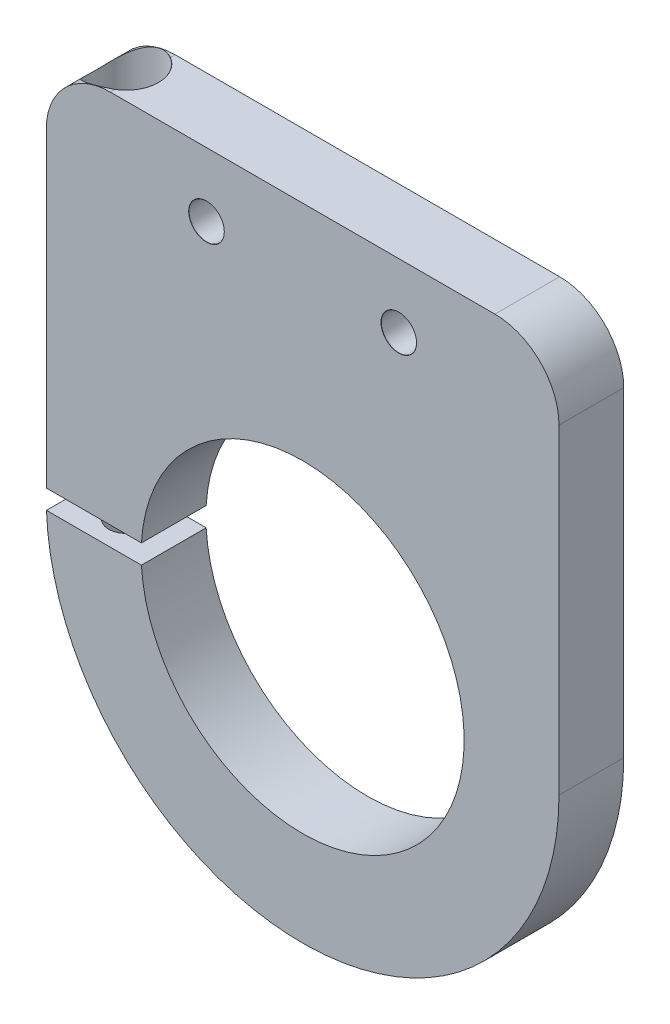
SolidWorks part; units mm, degrees
ref_plane "Front Plane" through (0, 0, 0) normal (0, 0, 1) x (1, 0, 0)
ref_plane "Top Plane" through (0, 0, 0) normal (0, 1, 0) x (1, 0, 0)
ref_plane "Right Plane" through (0, 0, 0) normal (1, 0, 0) x (0, 0, -1)
sketch "Sketch2" plane through (0, 0, 0) normal (0, 0, 1) x (1, 0, 0)
  line L0 (-40, 0) -> (-40, 60)
  line L1 (-40, 60) -> (40, 60)
  line L2 (40, 60) -> (40, 0)
  line L3 (40, 0) -> (-40, 0)
  circle A0 centre (0, 0) radius 40
  circle A1 centre (0, 0) radius 25.2
  dimension "D1" = 50.4
  dimension "D2" = 80
  dimension "D3" = 60
extrude "Boss-Extrude1" add sketch "Sketch2" along normal blind 10.1 contours A0 L2 L1 L0 | A1 L3 A0 | A1 L3 A0 region at (0, 39.1056, 0) region at (0, 44.3137, 0) region at (-32.6, -0.8944, 0)
sketch "Sketch3" plane through (0, 0, 10.1) normal (0, 0, 1) x (1, 0, 0)
  line L0 (-40, 0) -> (-40, 60) construction
  line L1 (-40, 1.5) -> (-25.1553, 1.5)
  line L2 (-40, 1.5) -> (-40, -1.5)
  line L3 (-40, -1.5) -> (-25.1553, -1.5)
  line L4 (-25.1553, 1.5) -> (-25.1553, -1.5)
  circle A2 centre (0, 0) radius 25.2 construction
  point P4 (-25.1553, 0)
  dimension "D1" = 3
extrude "Cut-Extrude1" cut sketch "Sketch3" against normal through all
sketch "Sketch11" plane through (0, 60, 0) normal (0, 1, 0) x (1, 0, 0)
  line L1 (-39.9719, -10.1) -> (-25.1553, -10.1) construction
  line L2 (-40, -10.1) -> (-40, 0) construction
  point P0 (-32.5636, -5.05)
  point P10 (-32.5636, -10.1)
  point P13 (-40, -5.05)
hole_wizard "CBORE for M5 SHCS3" positions "Sketch11" profile "Sketch10" counterbore size "M5" standard "ANSI Metric" end condition through all
sketch "Sketch10" plane through (-32.5636, 60, 5.05) normal (1, 0, 0) x (0, 0, 1)
  line L0 (0, 0) -> (0, 100)
  line L1 (0, 100) -> (2.75, 100)
  line L3 (2.75, 100) -> (2.75, 10)
  line L4 (5, 10) -> (2.75, 10)
  line L5 (5, 10) -> (5, 0.025)
  line L6 (5, 0.025) -> (5.025, 0)
  line L7 (5.025, 0) -> (0, 0)
  line L8 (-5, 0.025) -> (-5.025, 0) construction
  line L11 (0, -6.35) -> (0, 107.95) construction
  dimension "Thru Hole Dia." = 5.5
  dimension "Thru Hole Depth" = 100
  dimension "C'Bore Dia." = 10
  dimension "C'Bore Depth" = 10
  dimension "Near C'Sink Dia." = 10.05
  dimension "Near C'Sink Angle" = 90
sketch "Sketch17" plane through (0, 0, 10.1) normal (0, 0, 1) x (1, 0, 0)
  line L0 (-15, 50) -> (15, 50) construction
  line L2 (-40, 60) -> (40, 60) construction
  point P0 (-15, 50)
  point P2 (15, 50)
  point P9 (0, 50)
  dimension "D1" = 30
  dimension "D2" = 10
hole_wizard "M5 Clearance Hole1" positions "Sketch17" profile "Sketch15" hole size "M5" standard "ANSI Metric" end condition through all
sketch "Sketch15" plane through (-15, 50, 10.1) normal (1, 0, 0) x (0, -1, 0)
  line L0 (0, 0) -> (0, 10.1)
  line L1 (0, 10.1) -> (2.75, 10.1)
  line L2 (2.75, 10.1) -> (2.75, 0.025)
  line L3 (2.75, 0.025) -> (2.775, 0)
  line L5 (2.775, 0) -> (0, 0)
  line L6 (-2.75, 0.025) -> (-2.775, 0) construction
  line L11 (0, -6.35) -> (0, 107.95) construction
  dimension "Thru Hole Dia." = 5.5
  dimension "Thru Hole Depth" = 10.1
  dimension "Near C'Sink Dia." = 5.55
  dimension "Near C'Sink Angle" = 90
fillet "Fillet1" radius 10 2 edges at (-40, 60, 5.05) (40, 60, 5.05)
ref_plane "Plane1" through (0, -16.5, 0) normal (0, 1, 0) x (1, 0, 0)
sketch "Sketch18" plane through (0, -16.5, 0) normal (0, 1, 0) x (1, 0, 0)
  line L1 (-27.8293, -5.05) -> (-30.1965, -0.95)
  line L2 (-30.1965, -0.95) -> (-34.9307, -0.95)
  line L3 (-34.9307, -0.95) -> (-37.2979, -5.05)
  line L4 (-37.2979, -5.05) -> (-34.9307, -9.15)
  line L5 (-34.9307, -9.15) -> (-30.1965, -9.15)
  line L6 (-30.1965, -9.15) -> (-27.8293, -5.05)
  circle A0 centre (-32.5636, -5.05) radius 4.1 construction
  circle A1 centre (-32.5636, -5.05) radius 2.75 construction
  point P15 (-32.5636, -0.95)
  dimension "D1" = 8.2
extrude "Cut-Extrude2" cut sketch "Sketch18" against normal through all
